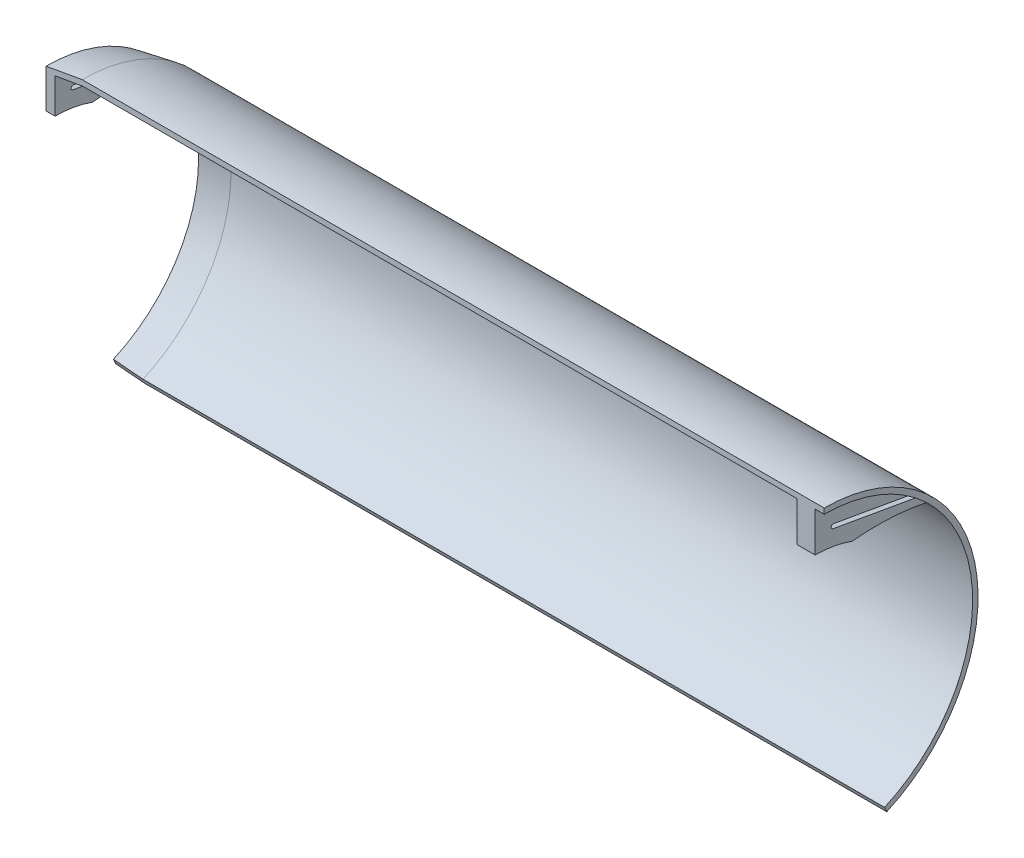
SolidWorks part; units mm, degrees
material "PETG"
ref_plane "Front Plane" through (0, 0, 0) normal (0, 0, 1) x (1, 0, 0)
ref_plane "Top Plane" through (0, 0, 0) normal (0, 1, 0) x (1, 0, 0)
ref_plane "Right Plane" through (0, 0, 0) normal (1, 0, 0) x (0, 0, -1)
curve "Curve1"
  spline degree 3 poles (0, 0, 0) (-0.0123, 3.8916, 0) (-0.0274, 8.685, 0) (0.3616, 14.0857, 0) (0.5761, 16.0905, 0) (0.7825, 17.6048, 0) (0.9862, 18.8543, 0) (1.1887, 19.9315, 0) (1.3904, 20.8857, 0) (1.5917, 21.7465, 0) (1.7927, 22.5337, 0) (1.9935, 23.2611, 0) (2.1942, 23.9386, 0) (2.3947, 24.5739, 0) (2.5952, 25.1728, 0) (2.7956, 25.7401, 0) (2.9959, 26.2796, 0) (3.1962, 26.7943, 0) (3.3965, 27.2868, 0) (3.5967, 27.7594, 0) (3.7969, 28.2139, 0) (3.9971, 28.6519, 0) (4.1973, 29.0748, 0) (4.3974, 29.4838, 0) (4.5976, 29.8799, 0) (4.7977, 30.2641, 0) (4.9978, 30.6373, 0) (5.1979, 31.0001, 0) (5.398, 31.3533, 0) (5.5981, 31.6974, 0) (5.7982, 32.033, 0) (5.9983, 32.3606, 0) (6.1984, 32.6807, 0) (6.3985, 32.9935, 0) (6.5985, 33.2996, 0) (6.7986, 33.5993, 0) (6.9986, 33.8929, 0) (7.1987, 34.1806, 0) (7.3987, 34.4628, 0) (7.5988, 34.7397, 0) (7.7988, 35.0115, 0) (7.9989, 35.2785, 0) (8.1989, 35.5408, 0) (8.399, 35.7988, 0) (8.599, 36.0524, 0) (8.799, 36.3019, 0) (8.9991, 36.5476, 0) (9.1991, 36.7894, 0) (9.3991, 37.0275, 0) (9.5992, 37.2622, 0) (9.7992, 37.4934, 0) (9.9992, 37.7214, 0) (10.1992, 37.9461, 0) (10.3993, 38.1679, 0) (10.5993, 38.3866, 0) (10.7993, 38.6025, 0) (10.9993, 38.8156, 0) (11.1993, 39.026, 0) (11.3994, 39.2338, 0) (11.5994, 39.4391, 0) (11.7994, 39.6419, 0) (11.9994, 39.8422, 0) (12.1994, 40.0403, 0) (12.3995, 40.2361, 0) (12.5995, 40.4297, 0) (12.7995, 40.6212, 0) (12.9995, 40.8106, 0) (13.1995, 40.998, 0) (13.3995, 41.1834, 0) (13.5995, 41.3668, 0) (13.7995, 41.5484, 0) (13.9996, 41.7281, 0) (14.1996, 41.9061, 0) (14.3996, 42.0823, 0) (14.5996, 42.2568, 0) (14.7996, 42.4296, 0) (14.9996, 42.6008, 0) (15.1996, 42.7705, 0) (15.3996, 42.9385, 0) (15.5996, 43.1051, 0) (15.7996, 43.2701, 0) (15.9997, 43.4337, 0) (16.1997, 43.5959, 0) (16.3997, 43.7567, 0) (16.5997, 43.9161, 0) (16.7997, 44.0742, 0) (16.9997, 44.2309, 0) (17.1997, 44.3864, 0) (17.3997, 44.5406, 0) (17.5997, 44.6936, 0) (17.7997, 44.8453, 0) (17.9997, 44.9959, 0) (18.1997, 45.1453, 0) (18.3997, 45.2936, 0) (18.5997, 45.4407, 0) (18.7997, 45.5868, 0) (18.9997, 45.7317, 0) (19.1998, 45.8756, 0) (19.3998, 46.0185, 0) (19.5998, 46.1603, 0) (19.7998, 46.3011, 0) (19.9998, 46.4409, 0) (20.1998, 46.5797, 0) (20.3998, 46.7176, 0) (20.5998, 46.8546, 0) (20.7998, 46.9906, 0) (20.9998, 47.1257, 0) (21.1998, 47.2599, 0) (21.3998, 47.3932, 0) (21.5998, 47.5256, 0) (21.7998, 47.6572, 0) (21.9998, 47.788, 0) (22.1998, 47.9179, 0) (22.3998, 48.047, 0) (22.5998, 48.1753, 0) (22.7998, 48.3028, 0) (22.9998, 48.4295, 0) (23.1998, 48.5555, 0) (23.3998, 48.6807, 0) (23.5998, 48.8051, 0) (23.7998, 48.9288, 0) (23.9998, 49.0518, 0) (24.1998, 49.1741, 0) (24.3998, 49.2957, 0) (24.5998, 49.4165, 0) (24.7999, 49.5367, 0) (24.9999, 49.6562, 0) (25.1999, 49.7751, 0) (25.3999, 49.8933, 0) (25.5999, 50.0108, 0) (25.7999, 50.1277, 0) (25.9999, 50.2439, 0) (26.1999, 50.3596, 0) (26.3999, 50.4746, 0) (26.5999, 50.589, 0) (26.7999, 50.7028, 0) (26.9999, 50.8161, 0) (27.1999, 50.9287, 0) (27.3999, 51.0407, 0) (27.5999, 51.1522, 0) (27.7999, 51.2631, 0) (27.9999, 51.3735, 0) (28.1999, 51.4833, 0) (28.3999, 51.5926, 0) (28.5999, 51.7013, 0) (28.7999, 51.8095, 0) (28.9999, 51.9172, 0) (29.1999, 52.0243, 0) (29.3999, 52.131, 0) (29.5999, 52.2371, 0) (29.7999, 52.3428, 0) (29.9999, 52.4479, 0) (30.1999, 52.5526, 0) (30.3999, 52.6567, 0) (30.5999, 52.7604, 0) (30.7999, 52.8636, 0) (30.9999, 52.9664, 0) (31.1999, 53.0687, 0) (31.3999, 53.1705, 0) (31.5999, 53.2719, 0) (31.7999, 53.3728, 0) (31.9999, 53.4733, 0) (32.1999, 53.5733, 0) (32.3999, 53.6729, 0) (32.5999, 53.7721, 0) (32.7999, 53.8709, 0) (32.9999, 53.9692, 0) (33.1999, 54.0671, 0) (33.3999, 54.1646, 0) (33.5999, 54.2617, 0) (33.7999, 54.3584, 0) (33.9999, 54.4547, 0) (34.1999, 54.5506, 0) (34.3999, 54.6461, 0) (34.5999, 54.7412, 0) (34.7999, 54.836, 0) (34.9999, 54.9303, 0) (35.1999, 55.0243, 0) (35.3999, 55.1179, 0) (35.5999, 55.2111, 0) (35.7999, 55.304, 0) (35.9999, 55.3965, 0) (36.1999, 55.4887, 0) (36.3999, 55.5805, 0) (36.5999, 55.6719, 0) (36.7999, 55.763, 0) (36.9999, 55.8537, 0) (37.1999, 55.9441, 0) (37.3999, 56.0342, 0) (37.5999, 56.1239, 0) (37.7999, 56.2133, 0) (37.9999, 56.3024, 0) (38.1999, 56.3911, 0) (38.3999, 56.4795, 0) (38.5999, 56.5676, 0) (38.7999, 56.6554, 0) (38.9999, 56.7428, 0) (39.1999, 56.83, 0) (39.3999, 56.9168, 0) (39.5999, 57.0033, 0) (39.7999, 57.0896, 0) (39.9999, 57.1755, 0) (40.1999, 57.2611, 0) (40.3999, 57.3464, 0) (40.5999, 57.4314, 0) (40.7999, 57.5161, 0) (40.9999, 57.6006, 0) (41.1999, 57.6847, 0) (41.3999, 57.7686, 0) (41.6, 57.8522, 0) (41.8, 57.9355, 0) (42, 58.0185, 0) (42.2, 58.1012, 0) (42.4, 58.1837, 0) (42.6, 58.2659, 0) (42.8, 58.3479, 0) (43, 58.4295, 0) (43.2, 58.5109, 0) (43.4, 58.592, 0) (43.6, 58.6729, 0) (43.8, 58.7535, 0) (44, 58.8339, 0) (44.2, 58.914, 0) (44.4, 58.9938, 0) (44.6, 59.0734, 0) (44.8, 59.1528, 0) (45, 59.2319, 0) (45.2, 59.3107, 0) (45.4, 59.3893, 0) (45.6, 59.4677, 0) (45.8, 59.5458, 0) (46, 59.6237, 0) (46.2, 59.7014, 0) (46.4, 59.7788, 0) (46.6, 59.856, 0) (46.8, 59.9329, 0) (47, 60.0096, 0) (47.2, 60.0861, 0) (47.4, 60.1624, 0) (47.6, 60.2385, 0) (47.8, 60.3143, 0) (48, 60.3899, 0) (48.2, 60.4652, 0) (48.4, 60.5404, 0) (48.6, 60.6153, 0) (48.8, 60.6901, 0) (49, 60.7646, 0) (49.2, 60.8389, 0) (49.4, 60.913, 0) (49.6, 60.9869, 0) (49.8, 61.0605, 0) (50, 61.134, 0) (50.2, 61.2072, 0) (50.4, 61.2803, 0) (50.6, 61.3531, 0) (50.8, 61.4258, 0) (51, 61.4982, 0) (51.2, 61.5705, 0) (51.4, 61.6426, 0) (51.6, 61.7144, 0) (51.8, 61.7861, 0) (52, 61.8575, 0) (52.2, 61.9288, 0) (52.4, 61.9999, 0) (52.6, 62.0708, 0) (52.8, 62.1415, 0) (53, 62.212, 0) (53.2, 62.2824, 0) (53.4, 62.3525, 0) (53.6, 62.4225, 0) (53.8, 62.4923, 0) (54, 62.5619, 0) (54.2, 62.6313, 0) (54.4, 62.7006, 0) (54.6, 62.7696, 0) (54.8, 62.8385, 0) (55, 62.9072, 0) (55.2, 62.9758, 0) (55.4, 63.0441, 0) (55.6, 63.1123, 0) (55.8, 63.1803, 0) (56, 63.2482, 0) (56.2, 63.3159, 0) (56.4, 63.3834, 0) (56.6, 63.4507, 0) (56.8, 63.5179, 0) (57, 63.5849, 0) (57.2, 63.6518, 0) (57.4, 63.7185, 0) (57.6, 63.785, 0) (57.8, 63.8513, 0) (58, 63.9175, 0) (58.2, 63.9836, 0) (58.4, 64.0495, 0) (58.6, 64.1152, 0) (58.8, 64.1808, 0) (59, 64.2462, 0) (59.2, 64.3114, 0) (59.4, 64.3765, 0) (59.6, 64.4415, 0) (59.8, 64.5063, 0) (60, 64.5709, 0) (60.2, 64.6354, 0) (60.4, 64.6998, 0) (60.6, 64.764, 0) (60.8, 64.828, 0) (61, 64.8919, 0) (61.2, 64.9557, 0) (61.4, 65.0193, 0) (61.6, 65.0827, 0) (61.8, 65.1461, 0) (62, 65.2092, 0) (62.2, 65.2723, 0) (62.4, 65.3352, 0) (62.6, 65.3979, 0) (62.8, 65.4605, 0) (63, 65.523, 0) (63.2, 65.5853, 0) (63.4, 65.6475, 0) (63.6, 65.7096, 0) (63.8, 65.7715, 0) (64, 65.8333, 0) (64.2, 65.895, 0) (64.4, 65.9565, 0) (64.6, 66.0179, 0) (64.8, 66.0791, 0) (65, 66.1402, 0) (65.2, 66.2012, 0) (65.4, 66.2621, 0) (65.6, 66.3228, 0) (65.8, 66.3834, 0) (66, 66.4439, 0) (66.2, 66.5042, 0) (66.4, 66.5644, 0) (66.6, 66.6245, 0) (66.8, 66.6845, 0) (67, 66.7443, 0) (67.2, 66.804, 0) (67.4, 66.8636, 0) (67.6, 66.923, 0) (67.8, 66.9824, 0) (68, 67.0416, 0) (68.2, 67.1007, 0) (68.4, 67.1597, 0) (68.6, 67.2185, 0) (68.8, 67.2772, 0) (69, 67.3359, 0) (69.2, 67.3943, 0) (69.4, 67.4527, 0) (69.6, 67.511, 0) (69.8, 67.5691, 0) (70, 67.6271, 0) (70.2, 67.6851, 0) (70.4, 67.7428, 0) (70.6, 67.8005, 0) (70.8, 67.8581, 0) (71, 67.9155, 0) (71.2, 67.9729, 0) (71.4, 68.0301, 0) (71.6, 68.0872, 0) (71.8, 68.1442, 0) (72, 68.2011, 0) (72.2, 68.2579, 0) (72.4, 68.3145, 0) (72.6, 68.3711, 0) (72.8, 68.4276, 0) (73, 68.4839, 0) (73.2, 68.5401, 0) (73.4, 68.5963, 0) (73.6, 68.6523, 0) (73.8, 68.7082, 0) (74, 68.764, 0) (74.2, 68.8197, 0) (74.4, 68.8753, 0) (74.6, 68.9308, 0) (74.8, 68.9862, 0) (75, 69.0415, 0) (75.2, 69.0966, 0) (75.4, 69.1517, 0) (75.6, 69.2067, 0) (75.8, 69.2616, 0) (76, 69.3164, 0) (76.2, 69.371, 0) (76.4, 69.4256, 0) (76.6, 69.4801, 0) (76.8, 69.5344, 0) (77, 69.5887, 0) (77.2, 69.6429, 0) (77.4, 69.697, 0) (77.6, 69.751, 0) (77.8, 69.8048, 0) (78, 69.8586, 0) (78.2, 69.9123, 0) (78.4, 69.9659, 0) (78.6, 70.0194, 0) (78.8, 70.0728, 0) (79, 70.1261, 0) (79.2, 70.1793, 0) (79.4, 70.2324, 0) (79.6, 70.2855, 0) (79.8, 70.3384, 0) (80, 70.3912, 0) (80.2, 70.444, 0) (80.4, 70.4966, 0) (80.6, 70.5492, 0) (80.8, 70.6017, 0) (81, 70.6541, 0) (81.2, 70.7064, 0) (81.4, 70.7586, 0) (81.6, 70.8107, 0) (81.8, 70.8627, 0) (82, 70.9146, 0) (82.2, 70.9665, 0) (82.4, 71.0182, 0) (82.6, 71.0699, 0) (82.8, 71.1215, 0) (83, 71.173, 0) (83.2, 71.2244, 0) (83.4, 71.2757, 0) (83.6, 71.3269, 0) (83.8, 71.3781, 0) (84, 71.4291, 0) (84.2, 71.4801, 0) (84.4, 71.531, 0) (84.6, 71.5818, 0) (84.8, 71.6325, 0) (85, 71.6832, 0) (85.2, 71.7337, 0) (85.4, 71.7842, 0) (85.6, 71.8346, 0) (85.8, 71.8849, 0) (86, 71.9351, 0) (86.2, 71.9853, 0) (86.4, 72.0354, 0) (86.6, 72.0853, 0) (86.8, 72.1352, 0) (87, 72.1851, 0) (87.2, 72.2348, 0) (87.4, 72.2845, 0) (87.6, 72.3341, 0) (87.8, 72.3836, 0) (88, 72.433, 0) (88.2, 72.4823, 0) (88.4, 72.5316, 0) (88.6, 72.5808, 0) (88.8, 72.6299, 0) (89, 72.6789, 0) (89.2, 72.7279, 0) (89.4, 72.7768, 0) (89.6, 72.8256, 0) (89.8, 72.8743, 0) (90, 72.923, 0) (90.2, 72.9716, 0) (90.4, 73.0201, 0) (90.6, 73.0685, 0) (90.8, 73.1168, 0) (91, 73.1651, 0) (91.2, 73.2133, 0) (91.4, 73.2614, 0) (91.6, 73.3095, 0) (91.8, 73.3575, 0) (92, 73.4054, 0) (92.2, 73.4532, 0) (92.4, 73.501, 0) (92.6, 73.5487, 0) (92.8, 73.5963, 0) (93, 73.6439, 0) (93.2, 73.6913, 0) (93.4, 73.7387, 0) (93.6, 73.7861, 0) (93.8, 73.8333, 0) (94, 73.8805, 0) (94.2, 73.9276, 0) (94.4, 73.9747, 0) (94.6, 74.0217, 0) (94.8, 74.0686, 0) (95, 74.1154, 0) (95.2, 74.1622, 0) (95.4, 74.2089, 0) (95.6, 74.2556, 0) (95.8, 74.3021, 0) (96, 74.3486, 0) (96.2, 74.3951, 0) (96.4, 74.4414, 0) (96.6, 74.4877, 0) (96.8, 74.534, 0) (97, 74.5801, 0) (97.2, 74.6262, 0) (97.4, 74.6723, 0) (97.6, 74.7182, 0) (97.8, 74.7641, 0) (98, 74.81, 0) (98.2, 74.8557, 0) (98.4, 74.9014, 0) (98.6, 74.9471, 0) (98.8, 74.9926, 0) (99, 75.0382, 0) (99.2, 75.0836, 0) (99.4, 75.129, 0) (99.6, 75.1743, 0) (99.8, 75.2196, 0) (100, 75.2647, 0) (100.2, 75.3099, 0) (100.4, 75.3549, 0) (100.6, 75.3999, 0) (100.8, 75.4449, 0) (101, 75.4898, 0) (101.2, 75.5346, 0) (101.4, 75.5793, 0) (101.6, 75.624, 0) (101.8, 75.6686, 0) (102, 75.7132, 0) (102.2, 75.7577, 0) (102.4, 75.8022, 0) (102.6, 75.8465, 0) (102.8, 75.8909, 0) (103, 75.9351, 0) (103.2, 75.9793, 0) (103.4, 76.0235, 0) (103.6, 76.0676, 0) (103.8, 76.1116, 0) (104, 76.1556, 0) (104.2, 76.1995, 0) (104.4, 76.2433, 0) (104.6, 76.2871, 0) (104.8, 76.3308, 0) (105, 76.3745, 0) (105.2, 76.4181, 0) (105.4, 76.4617, 0) (105.6, 76.5052, 0) (105.8, 76.5486, 0) (106, 76.592, 0) (106.2, 76.6353, 0) (106.4, 76.6786, 0) (106.6, 76.7218, 0) (106.8, 76.7649, 0) (107, 76.808, 0) (107.2, 76.8511, 0) (107.4, 76.8941, 0) (107.6, 76.937, 0) (107.8, 76.9799, 0) (108, 77.0227, 0) (108.2, 77.0655, 0) (108.4, 77.1082, 0) (108.6, 77.1508, 0) (108.8, 77.1934, 0) (109, 77.236, 0) (109.2, 77.2784, 0) (109.4, 77.3209, 0) (109.6, 77.3633, 0) (109.8, 77.4056, 0) (110, 77.4479, 0) (110.2, 77.4901, 0) (110.4, 77.5322, 0) (110.6, 77.5743, 0) (110.8, 77.6164, 0) (111, 77.6584, 0) (111.2, 77.7004, 0) (111.4, 77.7423, 0) (111.6, 77.7841, 0) (111.8, 77.8259, 0) (112, 77.8676, 0) (112.2, 77.9093, 0) (112.4, 77.951, 0) (112.6, 77.9925, 0) (112.8, 78.0341, 0) (113, 78.0756, 0) (113.2, 78.117, 0) (113.4, 78.1584, 0) (113.6, 78.1997, 0) (113.8, 78.241, 0) (114, 78.2822, 0) (114.2, 78.3234, 0) (114.4, 78.3645, 0) (114.6, 78.4056, 0) (114.8, 78.4466, 0) (115, 78.4876, 0) (115.2, 78.5285, 0) (115.4, 78.5694, 0) (115.6, 78.6102, 0) (115.8, 78.651, 0) (116, 78.6917, 0) (116.2, 78.7324, 0) (116.4, 78.773, 0) (116.6, 78.8136, 0) (116.8, 78.8541, 0) (117, 78.8946, 0) (117.2, 78.935, 0) (117.4, 78.9754, 0) (117.6, 79.0158, 0) (117.8, 79.0561, 0) (118, 79.0963, 0) (118.2, 79.1365, 0) (118.4, 79.1766, 0) (118.6, 79.2167, 0) (118.8, 79.2568, 0) (119, 79.2968, 0) (119.2, 79.3368, 0) (119.4, 79.3767, 0) (119.6, 79.4165, 0) (119.8, 79.4564, 0) (120, 79.4961, 0) (120.2, 79.5358, 0) (120.4, 79.5755, 0) (120.6, 79.6152, 0) (120.8, 79.6547, 0) (121, 79.6943, 0) (121.2, 79.7338, 0) (121.4, 79.7732, 0) (121.6, 79.8126, 0) (121.8, 79.852, 0) (122, 79.8913, 0) (122.2, 79.9306, 0) (122.4, 79.9698, 0) (122.6, 80.009, 0) (122.8, 80.0481, 0) (123, 80.0872, 0) (123.2, 80.1262, 0) (123.4, 80.1652, 0) (123.6, 80.2042, 0) (123.8, 80.2431, 0) (124, 80.282, 0) (124.2, 80.3208, 0) (124.4, 80.3596, 0) (124.6, 80.3983, 0) (124.8, 80.437, 0) (125, 80.4757, 0) (125.2, 80.5143, 0) (125.4, 80.5528, 0) (125.6, 80.5914, 0) (125.8, 80.6298, 0) (126, 80.6683, 0) (126.2, 80.7067, 0) (126.4, 80.745, 0) (126.6, 80.7833, 0) (126.8, 80.8216, 0) (127, 80.8598, 0) (127.2, 80.898, 0) (127.4, 80.9361, 0) (127.6, 80.9742, 0) (127.8, 81.0123, 0) (128, 81.0503, 0) (128.2, 81.0883, 0) (128.4, 81.1262, 0) (128.6, 81.1641, 0) (128.8, 81.2019, 0) (129, 81.2397, 0) (129.2, 81.2775, 0) (129.4, 81.3152, 0) (129.6, 81.3529, 0) (129.8, 81.3906, 0) (130, 81.4282, 0) (130.2, 81.4657, 0) (130.4, 81.5032, 0) (130.6, 81.5407, 0) (130.8, 81.5782, 0) (131, 81.6156, 0) (131.2, 81.6529, 0) (131.4, 81.6902, 0) (131.6, 81.7275, 0) (131.8, 81.7648, 0) (132, 81.802, 0) (132.2, 81.8391, 0) (132.4, 81.8763, 0) (132.6, 81.9133, 0) (132.8, 81.9504, 0) (133, 81.9874, 0) (133.2, 82.0244, 0) (133.4, 82.0613, 0) (133.6, 82.0982, 0) (133.8, 82.135, 0) (134, 82.1718, 0) (134.2, 82.2086, 0) (134.4, 82.2454, 0) (134.6, 82.282, 0) (134.8, 82.3187, 0) (135, 82.3553, 0) (135.2, 82.3919, 0) (135.4, 82.4285, 0) (135.6, 82.465, 0) (135.8, 82.5014, 0) (136, 82.5379, 0) (136.2, 82.5743, 0) (136.4, 82.6106, 0) (136.6, 82.6469, 0) (136.8, 82.6832, 0) (137, 82.7195, 0) (137.2, 82.7557, 0) (137.4, 82.7919, 0) (137.6, 82.828, 0) (137.8, 82.8641, 0) (138, 82.9001, 0) (138.2, 82.9362, 0) (138.4, 82.9722, 0) (138.6, 83.0081, 0) (138.8, 83.044, 0) (139, 83.0799, 0) (139.2, 83.1158, 0) (139.4, 83.1516, 0) (139.6, 83.1873, 0) (139.8, 83.2231, 0) (140, 83.2588, 0) (140.2, 83.2944, 0) (140.4, 83.3301, 0) (140.6, 83.3657, 0) (140.8, 83.4012, 0) (141, 83.4367, 0) (141.2, 83.4722, 0) (141.4, 83.5077, 0) (141.6, 83.5431, 0) (141.8, 83.5785, 0) (142, 83.6138, 0) (142.2, 83.6491, 0) (142.4, 83.6844, 0) (142.6, 83.7197, 0) (142.8, 83.7549, 0) (143, 83.79, 0) (143.2, 83.8252, 0) (143.4, 83.8603, 0) (143.6, 83.8954, 0) (143.8, 83.9304, 0) (144, 83.9654, 0) (144.2, 84.0004, 0) (144.4, 84.0353, 0) (144.6, 84.0702, 0) (144.8, 84.1051, 0) (145, 84.1399, 0) (145.2, 84.1747, 0) (145.4, 84.2095, 0) (145.6, 84.2442, 0) (145.8, 84.2789, 0) (146, 84.3136, 0) (146.2, 84.3482, 0) (146.4, 84.3828, 0) (146.6, 84.4174, 0) (146.8, 84.4519, 0) (147, 84.4864, 0) (147.2, 84.5209, 0) (147.4, 84.5553, 0) (147.6, 84.5897, 0) (147.8, 84.6241, 0) (148, 84.6584, 0) (148.2, 84.6927, 0) (148.4, 84.727, 0) (148.6, 84.7612, 0) (148.8, 84.7954, 0) (149, 84.8296, 0) (149.2, 84.8638, 0) (149.4, 84.8979, 0) (149.6, 84.9319, 0) (149.8, 84.966, 0) (149.9333, 84.9887, 0) (150, 85, 0) knots 0 0 0 0 0.061462 0.075706 0.085548 0.093322 0.099856 0.105554 0.110643 0.115268 0.119525 0.123482 0.127192 0.130691 0.13401 0.137173 0.140199 0.143104 0.145901 0.148602 0.151215 0.15375 0.156213 0.158609 0.160946 0.163227 0.165456 0.167638 0.169775 0.171871 0.173928 0.17595 0.177937 0.179893 0.181819 0.183716 0.185587 0.187433 0.189255 0.191054 0.192831 0.194589 0.196326 0.198045 0.199747 0.201431 0.2031 0.204753 0.206391 0.208015 0.209626 0.211223 0.212808 0.214381 0.215942 0.217493 0.219032 0.220561 0.22208 0.22359 0.225091 0.226582 0.228065 0.229539 0.231006 0.232464 0.233915 0.235359 0.236795 0.238225 0.239648 0.241065 0.242475 0.243879 0.245277 0.24667 0.248057 0.249438 0.250814 0.252185 0.253551 0.254913 0.256269 0.257621 0.258968 0.260311 0.26165 0.262984 0.264315 0.265641 0.266964 0.268282 0.269598 0.270909 0.272217 0.273522 0.274823 0.276121 0.277416 0.278707 0.279996 0.281281 0.282564 0.283843 0.28512 0.286394 0.287666 0.288935 0.290201 0.291465 0.292726 0.293985 0.295241 0.296495 0.297747 0.298996 0.300243 0.301489 0.302732 0.303972 0.305211 0.306448 0.307683 0.308916 0.310147 0.311376 0.312604 0.313829 0.315053 0.316275 0.317495 0.318714 0.319931 0.321147 0.32236 0.323573 0.324783 0.325993 0.3272 0.328406 0.329611 0.330815 0.332017 0.333217 0.334416 0.335614 0.336811 0.338006 0.3392 0.340393 0.341584 0.342775 0.343964 0.345152 0.346339 0.347524 0.348709 0.349892 0.351074 0.352256 0.353436 0.354615 0.355793 0.35697 0.358146 0.359321 0.360495 0.361668 0.36284 0.364011 0.365182 0.366351 0.36752 0.368687 0.369854 0.37102 0.372185 0.373349 0.374512 0.375674 0.376836 0.377997 0.379157 0.380316 0.381475 0.382632 0.383789 0.384946 0.386101 0.387256 0.38841 0.389563 0.390716 0.391868 0.393019 0.39417 0.39532 0.396469 0.397618 0.398766 0.399913 0.40106 0.402206 0.403351 0.404496 0.40564 0.406784 0.407927 0.409069 0.410211 0.411353 0.412493 0.413633 0.414773 0.415912 0.417051 0.418189 0.419326 0.420463 0.4216 0.422736 0.423871 0.425006 0.426141 0.427275 0.428408 0.429541 0.430674 0.431806 0.432937 0.434068 0.435199 0.436329 0.437459 0.438588 0.439717 0.440846 0.441974 0.443101 0.444229 0.445355 0.446482 0.447608 0.448733 0.449858 0.450983 0.452107 0.453231 0.454355 0.455478 0.456601 0.457723 0.458845 0.459967 0.461088 0.462209 0.46333 0.46445 0.46557 0.46669 0.467809 0.468928 0.470046 0.471164 0.472282 0.4734 0.474517 0.475634 0.47675 0.477866 0.478982 0.480098 0.481213 0.482328 0.483443 0.484557 0.485671 0.486785 0.487898 0.489011 0.490124 0.491237 0.492349 0.493461 0.494573 0.495684 0.496796 0.497906 0.499017 0.500127 0.501237 0.502347 0.503457 0.504566 0.505675 0.506784 0.507892 0.509001 0.510109 0.511216 0.512324 0.513431 0.514538 0.515645 0.516752 0.517858 0.518964 0.52007 0.521175 0.522281 0.523386 0.524491 0.525595 0.5267 0.527804 0.528908 0.530012 0.531116 0.532219 0.533322 0.534425 0.535528 0.53663 0.537733 0.538835 0.539937 0.541038 0.54214 0.543241 0.544342 0.545443 0.546544 0.547644 0.548745 0.549845 0.550945 0.552044 0.553144 0.554243 0.555342 0.556441 0.55754 0.558639 0.559737 0.560836 0.561934 0.563032 0.564129 0.565227 0.566324 0.567421 0.568518 0.569615 0.570712 0.571809 0.572905 0.574001 0.575097 0.576193 0.577289 0.578384 0.57948 0.580575 0.58167 0.582765 0.58386 0.584954 0.586049 0.587143 0.588237 0.589331 0.590425 0.591519 0.592612 0.593706 0.594799 0.595892 0.596985 0.598078 0.59917 0.600263 0.601355 0.602448 0.60354 0.604632 0.605724 0.606815 0.607907 0.608998 0.61009 0.611181 0.612272 0.613363 0.614453 0.615544 0.616635 0.617725 0.618815 0.619905 0.620995 0.622085 0.623175 0.624265 0.625354 0.626443 0.627533 0.628622 0.629711 0.6308 0.631888 0.632977 0.634066 0.635154 0.636242 0.637331 0.638419 0.639507 0.640594 0.641682 0.64277 0.643857 0.644945 0.646032 0.647119 0.648206 0.649293 0.65038 0.651467 0.652553 0.65364 0.654726 0.655813 0.656899 0.657985 0.659071 0.660157 0.661243 0.662328 0.663414 0.664499 0.665585 0.66667 0.667755 0.66884 0.669925 0.67101 0.672095 0.67318 0.674264 0.675349 0.676433 0.677518 0.678602 0.679686 0.68077 0.681854 0.682938 0.684022 0.685105 0.686189 0.687272 0.688356 0.689439 0.690522 0.691605 0.692688 0.693771 0.694854 0.695937 0.69702 0.698102 0.699185 0.700267 0.70135 0.702432 0.703514 0.704596 0.705678 0.70676 0.707842 0.708924 0.710006 0.711087 0.712169 0.71325 0.714332 0.715413 0.716494 0.717575 0.718656 0.719737 0.720818 0.721899 0.72298 0.724061 0.725141 0.726222 0.727302 0.728382 0.729463 0.730543 0.731623 0.732703 0.733783 0.734863 0.735943 0.737023 0.738103 0.739182 0.740262 0.741341 0.742421 0.7435 0.744579 0.745659 0.746738 0.747817 0.748896 0.749975 0.751054 0.752133 0.753211 0.75429 0.755369 0.756447 0.757526 0.758604 0.759682 0.760761 0.761839 0.762917 0.763995 0.765073 0.766151 0.767229 0.768307 0.769385 0.770462 0.77154 0.772618 0.773695 0.774773 0.77585 0.776927 0.778005 0.779082 0.780159 0.781236 0.782313 0.78339 0.784467 0.785544 0.786621 0.787698 0.788774 0.789851 0.790928 0.792004 0.793081 0.794157 0.795233 0.79631 0.797386 0.798462 0.799538 0.800614 0.80169 0.802766 0.803842 0.804918 0.805994 0.80707 0.808145 0.809221 0.810296 0.811372 0.812447 0.813523 0.814598 0.815674 0.816749 0.817824 0.818899 0.819974 0.821049 0.822124 0.823199 0.824274 0.825349 0.826424 0.827499 0.828573 0.829648 0.830723 0.831797 0.832872 0.833946 0.835021 0.836095 0.837169 0.838244 0.839318 0.840392 0.841466 0.84254 0.843614 0.844688 0.845762 0.846836 0.84791 0.848984 0.850058 0.851131 0.852205 0.853279 0.854352 0.855426 0.856499 0.857573 0.858646 0.859719 0.860793 0.861866 0.862939 0.864012 0.865085 0.866159 0.867232 0.868305 0.869378 0.87045 0.871523 0.872596 0.873669 0.874742 0.875814 0.876887 0.87796 0.879032 0.880105 0.881177 0.88225 0.883322 0.884395 0.885467 0.886539 0.887611 0.888684 0.889756 0.890828 0.8919 0.892972 0.894044 0.895116 0.896188 0.89726 0.898332 0.899404 0.900475 0.901547 0.902619 0.90369 0.904762 0.905834 0.906905 0.907977 0.909048 0.91012 0.911191 0.912262 0.913334 0.914405 0.915476 0.916548 0.917619 0.91869 0.919761 0.920832 0.921903 0.922974 0.924045 0.925116 0.926187 0.927258 0.928329 0.929399 0.93047 0.931541 0.932612 0.933682 0.934753 0.935823 0.936894 0.937965 0.939035 0.940105 0.941176 0.942246 0.943317 0.944387 0.945457 0.946527 0.947598 0.948668 0.949738 0.950808 0.951878 0.952948 0.954018 0.955088 0.956158 0.957228 0.958298 0.959368 0.960438 0.961508 0.962577 0.963647 0.964717 0.965786 0.966856 0.967926 0.968995 0.970065 0.971134 0.972204 0.973273 0.974343 0.975412 0.976481 0.977551 0.97862 0.979689 0.980759 0.981828 0.982897 0.983966 0.985035 0.986104 0.987173 0.988242 0.989311 0.99038 0.991449 0.992518 0.993587 0.994656 0.995725 0.996794 0.997863 0.998931 1 1 1 1
sketch "Sketch1" plane through (0, 0, 0) normal (0, 0, 1) x (1, 0, 0)
  line L0 (150, 85) -> (560, 85)
  line L1 (150.2533, 82) -> (560, 82)
  line L2 (560, 85) -> (560, 82)
  line L3 (0, 0) -> (3, 0)
  line L4 (3, 0.0095) -> (3, 0)
  line L5 (3, 0) -> (560, 0) construction
  line L6 (560, 0) -> (560, 82) construction
  line L8 (140, -75) -> (540, -75) construction
  line L9 (130, 78.3755) -> (135, 78.3755)
  line L10 (140, -75) -> (140, 75) construction
  line L11 (140, 75) -> (540, 75) construction
  line L12 (135, 79.3054) -> (135, 60)
  line L13 (135, 60) -> (130, 60)
  line L14 (130, 60) -> (130, 81.4281)
  line L15 (555, 60) -> (555, 82)
  line L16 (545, 82) -> (545, 60)
  line L17 (545, 60) -> (555, 60)
  line L18 (540, -75) -> (540, 75) construction
  line L19 (140, -75) -> (540, 75) construction
  line L20 (140, 75) -> (540, -75) construction
  spline S0 degree 3 poles (-1988.6566, -159.7184) (98.3599, -158.1291) (-5.7084, -70.1856) (0.3616, 14.0857) (0.5761, 16.0905) (0.7825, 17.6048) (0.9862, 18.8543) (1.1887, 19.9315) (1.3904, 20.8857) (1.5917, 21.7465) (1.7927, 22.5337) (1.9935, 23.2611) (2.2538, 24.14) (2.5806, 25.1462) (2.9836, 26.2595) (3.3859, 27.2713) (3.7877, 28.2016) (4.1891, 29.0648) (4.5903, 29.8717) (5.0533, 30.7478) (5.5832, 31.6835) (6.1854, 32.6697) (6.7872, 33.5906) (7.4515, 34.5461) (8.1828, 35.531) (8.9851, 36.54) (9.8503, 37.5625) (10.7826, 38.5957) (11.785, 39.6369) (12.851, 40.6804) (13.984, 41.7246) (15.1862, 42.7682) (16.388, 43.7553) (17.6544, 44.7435) (18.9876, 45.7315) (20.3892, 46.7179) (21.7905, 47.6579) (23.2571, 48.5984) (24.7904, 49.5382) (26.3916, 50.4762) (28.0583, 51.4122) (29.7917, 52.3451) (31.5927, 53.2742) (33.4594, 54.1996) (35.3929, 55.1207) (37.4597, 56.0672) (39.5933, 57.0066) (41.8602, 57.9666) (44.1937, 58.9175) (46.6606, 59.8853) (49.2604, 60.8677) (51.994, 61.8617) (54.861, 62.8656) (57.7946, 63.8556) (60.8615, 64.8536) (64.0615, 65.8584) (67.4615, 66.8882) (70.9951, 67.9202) (74.6621, 68.9539) (78.4621, 69.9886) (82.4622, 71.0404) (86.6623, 72.1071) (91.0624, 73.1864) (95.6625, 74.2764) (100.4626, 75.3753) (105.4628, 76.4816) (110.6629, 77.5938) (116.063, 78.7107) (121.6632, 79.8312) (127.5299, 80.9671) (133.6633, 82.1162) (140.0634, 83.2764) (145.1985, 84.1774) (148.3332, 84.7158) (149.3333, 84.8865) (149.6, 84.9319) (194.4783, 92.5723) (239.7917, 97.2513) (-50.3187, 2073.1568) knots -1.249314 -1.249314 -1.249314 -1.249314 0.061462 0.075706 0.085548 0.093322 0.099856 0.105554 0.110643 0.115268 0.119525 0.123482 0.127192 0.13401 0.140199 0.145901 0.151215 0.156213 0.160946 0.165456 0.171871 0.177937 0.183716 0.189255 0.196326 0.2031 0.209626 0.217493 0.225091 0.232464 0.241065 0.249438 0.257621 0.265641 0.274823 0.283843 0.292726 0.301489 0.311376 0.321147 0.330815 0.341584 0.352256 0.36284 0.374512 0.386101 0.398766 0.411353 0.425006 0.438588 0.453231 0.468928 0.484557 0.501237 0.517858 0.535528 0.554243 0.574001 0.593706 0.614453 0.636242 0.659071 0.682938 0.707842 0.733783 0.760761 0.788774 0.817824 0.84791 0.879032 0.912262 0.946527 0.981828 0.994656 0.996794 0.997863 0.998931 1.716252 1.716252 1.716252 1.716252 only from (0, 0) to (150, 85) construction
  spline S1 degree 3 poles (0, 0) (-0.0123, 3.8916) (-0.0274, 8.685) (0.3616, 14.0857) (0.5761, 16.0905) (0.7825, 17.6048) (0.9862, 18.8543) (1.1887, 19.9315) (1.3904, 20.8857) (1.5917, 21.7465) (1.7927, 22.5337) (1.9935, 23.2611) (2.2538, 24.14) (2.5806, 25.1462) (2.9836, 26.2595) (3.3859, 27.2713) (3.7877, 28.2016) (4.1891, 29.0648) (4.5903, 29.8717) (5.0533, 30.7478) (5.5832, 31.6835) (6.1854, 32.6697) (6.7872, 33.5906) (7.4515, 34.5461) (8.1828, 35.531) (8.9851, 36.54) (9.8503, 37.5625) (10.7826, 38.5957) (11.785, 39.6369) (12.851, 40.6804) (13.984, 41.7246) (15.1862, 42.7682) (16.388, 43.7553) (17.6544, 44.7435) (18.9876, 45.7315) (20.3892, 46.7179) (21.7905, 47.6579) (23.2571, 48.5984) (24.7904, 49.5382) (26.3916, 50.4762) (28.0583, 51.4122) (29.7917, 52.3451) (31.5927, 53.2742) (33.4594, 54.1996) (35.3929, 55.1207) (37.4597, 56.0672) (39.5933, 57.0066) (41.8602, 57.9666) (44.1937, 58.9175) (46.6606, 59.8853) (49.2604, 60.8677) (51.994, 61.8617) (54.861, 62.8656) (57.7946, 63.8556) (60.8615, 64.8536) (64.0615, 65.8584) (67.4615, 66.8882) (70.9951, 67.9202) (74.6621, 68.9539) (78.4621, 69.9886) (82.4622, 71.0404) (86.6623, 72.1071) (91.0624, 73.1864) (95.6625, 74.2764) (100.4626, 75.3753) (105.4628, 76.4816) (110.6629, 77.5938) (116.063, 78.7107) (121.6632, 79.8312) (127.5299, 80.9671) (133.6633, 82.1162) (140.0634, 83.2764) (145.1985, 84.1774) (148.3332, 84.7158) (149.4, 84.8979) (149.7333, 84.9547) (149.9333, 84.9887) (150, 85) knots 0 0 0 0 0.061462 0.075706 0.085548 0.093322 0.099856 0.105554 0.110643 0.115268 0.119525 0.123482 0.127192 0.13401 0.140199 0.145901 0.151215 0.156213 0.160946 0.165456 0.171871 0.177937 0.183716 0.189255 0.196326 0.2031 0.209626 0.217493 0.225091 0.232464 0.241065 0.249438 0.257621 0.265641 0.274823 0.283843 0.292726 0.301489 0.311376 0.321147 0.330815 0.341584 0.352256 0.36284 0.374512 0.386101 0.398766 0.411353 0.425006 0.438588 0.453231 0.468928 0.484557 0.501237 0.517858 0.535528 0.554243 0.574001 0.593706 0.614453 0.636242 0.659071 0.682938 0.707842 0.733783 0.760761 0.788774 0.817824 0.84791 0.879032 0.912262 0.946527 0.981828 0.994656 0.996794 0.998931 1 1 1 1
  spline S4 degree 1 poles (3, 0.0095) (150.2533, 82) knots 0 0 1 1 construction
  spline S5 degree 3 poles (3, 0.0095) (2.9938, 1.9694) (2.982, 5.9112) (3.1447, 11.6915) (3.6709, 17.3262) (4.8192, 22.7297) (6.752, 27.816) (10.434, 34.0689) (16.886, 40.7698) (26.3115, 47.2193) (36.5885, 52.5329) (47.3393, 57.0416) (62.0527, 62.2707) (80.8898, 67.7174) (103.8331, 73.1782) (119.8433, 76.4414) (128.9979, 78.1869) (130.8328, 78.5327) (132.4993, 78.8436) (134.1662, 79.1526) (140.0771, 80.2373) (145.5819, 81.205) (150.2533, 82) knots 0 0 0 0 0.031208 0.062417 0.093625 0.124833 0.156041 0.18725 0.249666 0.312083 0.374499 0.436916 0.499332 0.624165 0.748998 0.873831 0.883277 0.89671 0.903427 0.910144 0.923577 0.998664 0.998664 0.998664 0.998664
  point P8 (340, 0)
  dimension "D2" = 410
  dimension "D1" = 5
  dimension "D7" = 10
  dimension "D9" = 10
  dimension "D4" = 20
  dimension "D5" = 5
  dimension "D6" = 400
  dimension "D10" = 150
  dimension "D8" = 120
  dimension "D3" = 3
revolve "Revolve5" add sketch "Sketch1" angle 156 about L5 region at (344.8477, 83.4159, 0) region at (133.3296, 78.6861, 0) region at (132.5, 69.1877, 0) region at (550, 71, 0) reverse direction yes
ref_axis "Axis1" through (150, -77.6514, -34.5726) along (1, 0, 0)
ref_plane "Plane1" through (135, 0, 0) normal (1, 0, 0) x (0, 0, -1)
sketch "Sketch4" plane through (135, 0, 0) normal (-1, 0, 0) x (0, 0, 1)
  line L0 (0, 0) -> (-28.1672, 77.3887) construction
  line L1 (0, -89.4583) -> (0, 89.4583) construction
  line L2 (0, 60) -> (0, 82.3553)
  line L6 (0, 0) -> (-10.4189, 59.0885) construction
  line L7 (-57.113, 59.3338) -> (-9.8003, 67.6764)
  line L8 (-53.9452, 62.2279) -> (-10.1997, 69.9414)
  arc A1 (0, 82.3553) -> (-33.4969, -75.2353) centre (0, 0) ccw
  arc A2 (0, 82.3553) -> (-53.9452, 62.2279) centre (0, 0) ccw
  arc A5 (0, 60) -> (-24.4042, -54.8127) centre (0, 0) ccw construction
  arc A8 (0, 60) -> (-20.5212, 56.3816) centre (0, 0) ccw
  arc A9 (-9.8003, 67.6764) -> (-10.1997, 69.9414) centre (-10, 68.8089) ccw
  arc A10 (-20.5212, 56.3816) -> (-61.9052, 54.3153) centre (-34.5726, -77.6514) ccw
  arc A11 (-57.113, 59.3338) -> (-61.9052, 54.3153) centre (0, 0) ccw
  point P5 (-10.4189, 59.0885)
  point P14 (-20.5212, 56.3816)
  dimension "D2" = 8.35
  dimension "D3" = 2.3
  dimension "D4" = 10
  dimension "D1" = 20
extrude "Cut-Extrude2" cut sketch "Sketch4" along normal blind 170 flip side to cut
sketch "Sketch5" plane through (555, 0, 0) normal (1, 0, 0) x (0, 0, -1)
  line L0 (9.8003, 67.6764) -> (51.4774, 60.3275) construction
  line L1 (47.7475, 63.3207) -> (10.1997, 69.9414) construction
  line L6 (0, 85) -> (0, 82)
  line L8 (33.3524, -74.9107) -> (34.5726, -77.6514)
  line L9 (0, 85) -> (0, 60)
  line L10 (33.3524, -74.9107) -> (34.5726, -77.6514)
  line L11 (9.8003, 67.6764) -> (56.4827, 59.445)
  line L12 (53.2601, 62.3487) -> (10.1997, 69.9414)
  arc A0 (20.5212, 56.3816) -> (0, 60) centre (0, 0) ccw construction
  arc A1 (56.887, 55.2559) -> (20.5212, 56.3816) centre (34.5726, -77.6514) ccw construction
  arc A2 (33.3524, -74.9107) -> (0, 82) centre (0, 0) ccw
  arc A3 (34.5726, -77.6514) -> (0, 85) centre (0, 0) ccw
  arc A4 (33.3524, -74.9107) -> (61.3267, 54.4338) centre (0, 0) ccw
  arc A9 (34.5726, -77.6514) -> (0, 85) centre (0, 0) ccw
  arc A23 (10.1997, 69.9414) -> (9.8003, 67.6764) centre (10, 68.8089) ccw construction
  arc A24 (20.5212, 56.3816) -> (0, 60) centre (0, 0) ccw
  arc A27 (61.3267, 54.4338) -> (20.5212, 56.3816) centre (34.5726, -77.6514) ccw
  arc A34 (10.1997, 69.9414) -> (9.8003, 67.6764) centre (10, 68.8089) ccw
  arc A35 (56.4827, 59.445) -> (53.2601, 62.3487) centre (0, 0) ccw
  dimension "D1" = 0
extrude "Cut-Extrude3" cut sketch "Sketch5" against normal blind 10 and the other way through all flip side to cut
equation "\"CanSat_Len\"= 400mm"
equation "\"CanSat_Dia\"= 150mm"
equation "\"BodyTube_ID\"= 114mm"
equation "\"BodyTube_OD\"= 120mm"
equation "\"PayLoadBay_ID\"= 164mm"
equation "\"PayLoadBay_OD\"= 170mm"
equation "\"ParachuteBay_Pitch\"= 300mm"
equation "\"ElectronicsTray_PitchDist\"= 50mm"
equation "\"ElectronicsTray_Height\"= 140mm"
equation "\"MotorDia\"= 98mm"
equation "\"MotorLen\"=289mm"
equation "\"NosePlateDia\"= 156.6mm"
equation "\"D10@Sketch1\"=\"CanSat_Dia\""
equation "\"D6@Sketch1\"=\"CanSat_Len\""
